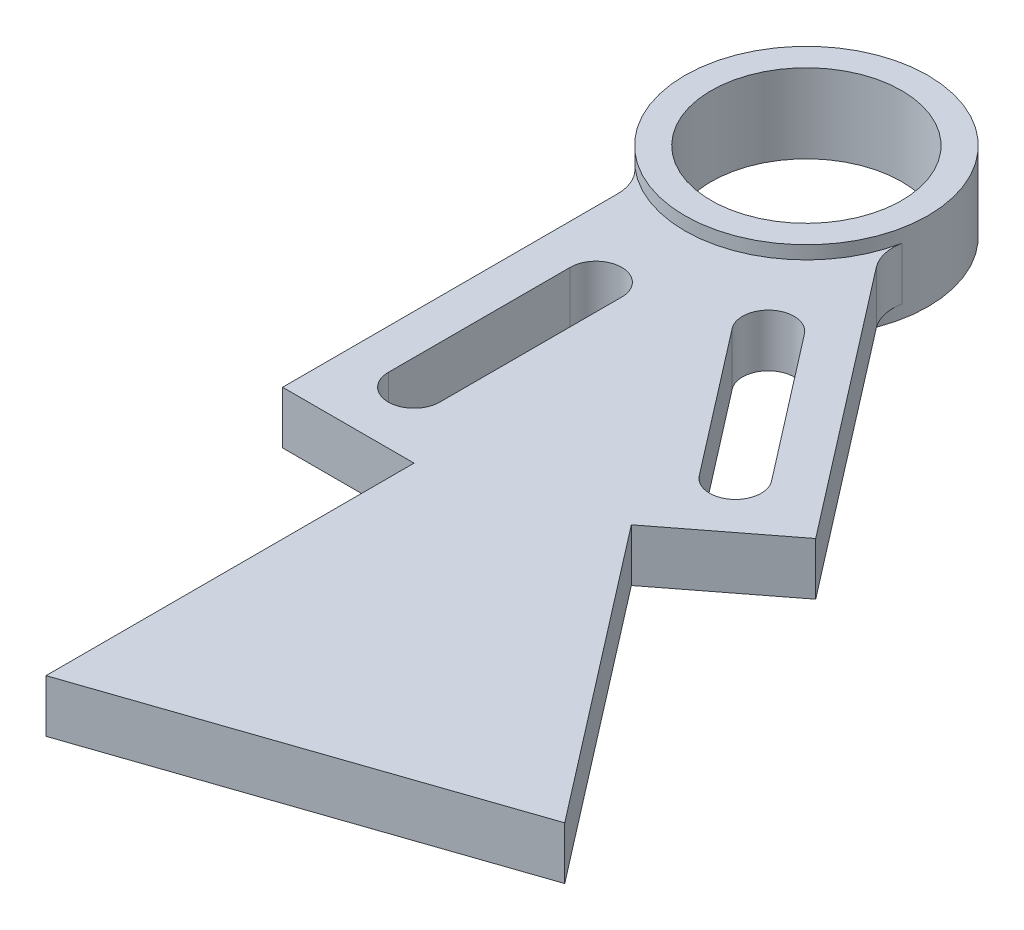
SolidWorks part; units mm, degrees
material "AISI 4130 Steel, normalized at 870C"
ref_plane "Front Plane" through (0, 0, 0) normal (0, 0, 1) x (1, 0, 0)
ref_plane "Top Plane" through (0, 0, 0) normal (0, 1, 0) x (1, 0, 0)
ref_plane "Right Plane" through (0, 0, 0) normal (1, 0, 0) x (0, 0, -1)
sketch "Sketch1" plane through (0, 0, 0) normal (0, 1, 0) x (1, 0, 0)
  line L0 (0, -50.4952) -> (0, -14.6812) construction
  line L1 (30.8439, -39.9802) -> (8.9677, -11.624) construction
  line L2 (0, -47.3837) -> (0, -25.4127) construction
  line L5 (-3.1115, -47.3837) -> (-3.1115, -25.4127)
  line L8 (-7.9375, -55.3212) -> (7.9375, -55.3212)
  line L9 (27.5071, -48.6497) -> (40.0764, -38.9528)
  line L10 (-7.9375, -55.3212) -> (-7.9375, -12.3505)
  line L11 (40.0764, -38.9528) -> (13.8286, -4.9302)
  line L12 (7.9375, -55.3212) -> (7.9375, -99.7712)
  line L13 (27.5071, -48.6497) -> (54.6585, -83.8436)
  line L14 (7.9375, -99.7712) -> (54.6585, -83.8436)
  line L15 (0, -14.6812) -> (0, 0) construction
  line L16 (0, -55.3212) -> (0, -50.4952) construction
  line L17 (33.7918, -43.8013) -> (30.8439, -39.9802)
  line L18 (3.1115, -47.3837) -> (3.1115, -25.4127)
  line L19 (15.5228, -20.1208) -> (28.9433, -37.5167) construction
  line L20 (17.9864, -18.2202) -> (31.4069, -35.6161)
  line L21 (13.0592, -22.0214) -> (26.4797, -39.4173)
  line L22 (8.9677, -11.624) -> (0, 0) construction
  line L23 (0, 0) -> (21.3094, -62.5075) construction
  line L25 (198.9178, -257.8397) -> (17.0665, -22.1219) construction
  line L27 (0, 0) -> (31.298, -91.8074) construction
  circle A0 centre (0, 0) radius 11.5062
  circle A1 centre (0, 0) radius 14.6812
  arc A2 (-3.1115, -47.3837) -> (3.1115, -47.3837) centre (0, -47.3837) ccw
  arc A3 (3.1115, -25.4127) -> (-3.1115, -25.4127) centre (0, -25.4127) ccw
  arc A4 (17.9864, -18.2202) -> (13.0592, -22.0214) centre (15.5228, -20.1208) ccw
  arc A5 (26.4797, -39.4173) -> (31.4069, -35.6161) centre (28.9433, -37.5167) ccw
  point P9 (0, -36.3982)
  point P14 (22.2331, -28.8188)
  point P23 (0, -55.3212)
  point P26 (33.7918, -43.8013)
  point P33 (0, -50.4952)
  point P36 (30.8439, -39.9802)
  point P38 (0, -22.3012)
  dimension "D2" = 29.3624
  dimension "D3" = 40.64
  dimension "D4" = 4.826
  dimension "D6" = 44.45
  dimension "D7" = 7.9375
  dimension "D5" = 4.826
  dimension "D8" = 7.62
  dimension "D9" = 66.04
extrude "Bearing extrude" add sketch "Sketch1" along normal mid plane 9.525 contours A1 A0 region at (-6.8368, 0, -12.521)
extrude "Boss-Extrude2" add sketch "Sketch1<5>" along normal mid plane 6.35 contours A1 L10 L8 L12 L14 L13 L9 L11 A4 A2 region at (19.0286, 0, 55.8173)
sketch "Sketch1<5>" plane through (0, 0, 0) normal (0, 1, 0) x (1, 0, 0) same geometry as "Sketch1"
sketch3d "Tab Point"
  line L0 (21.3094, 0, 62.5075) -> (21.3094, 22.225, 62.5075) construction
  line L1 (0, 0, 0) -> (21.3094, 0, 62.5075) construction
  line L2 (0, 0, 0) -> (31.298, 0, 91.8074) construction
  dimension "D1" = 22.225
fillet "Fillet1" radius 5.08 2 edges at (13.8286, 0, 4.9302) (-7.9375, 0, 12.3505)
equation "\"Apex_thickness\"= .25"
equation "\"Bearing_diameter\"= .906"
equation "\"A-arm_angle\"= 32.91"
equation "\"D1@Sketch1\"=\"Bearing_diameter\""
equation "\"D1@Boss-Extrude2\"= \"Apex_thickness\""
equation "\"apex slot\"= 1.4"
equation "\"tube diameter\"= 5 / 8"
